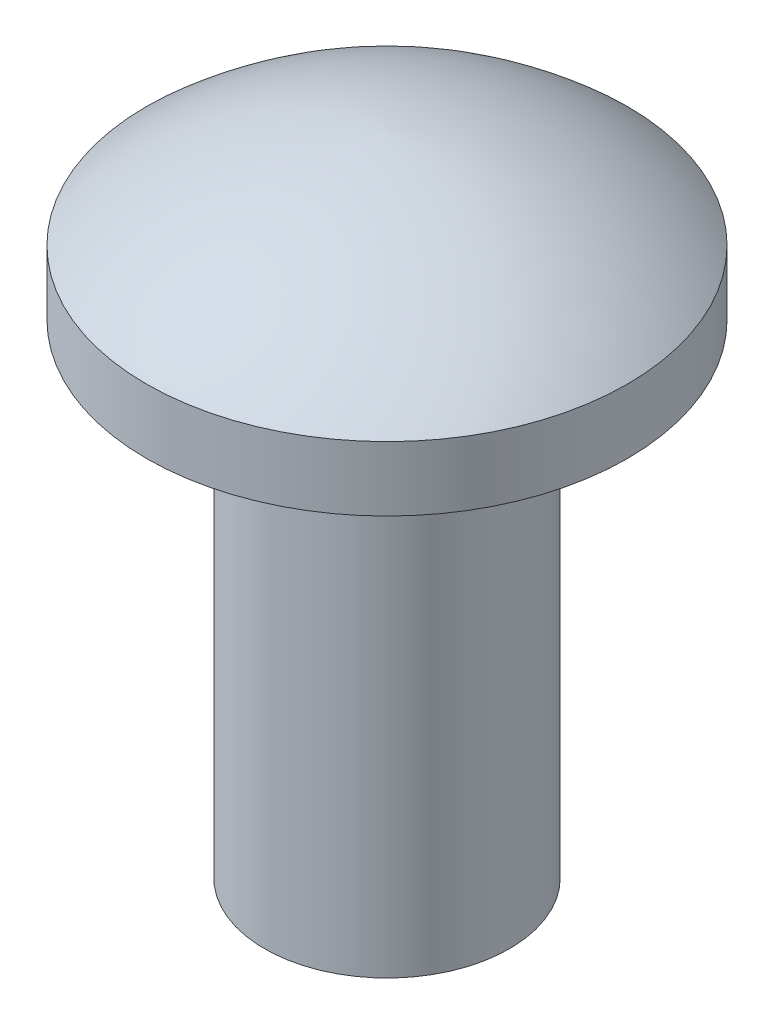
SolidWorks part; units mm, degrees
ref_plane "Front Plane" through (0, 0, 0) normal (0, 0, 1) x (1, 0, 0)
ref_plane "Top Plane" through (0, 0, 0) normal (0, 1, 0) x (1, 0, 0)
ref_plane "Right Plane" through (0, 0, 0) normal (1, 0, 0) x (0, 0, -1)
other "Center of Mass"
sketch "Sketch1" plane through (0, 0, 0) normal (0, 0, 1) x (1, 0, 0)
  line L0 (0, 0) -> (0, 12.7)
  line L1 (0, 0) -> (2.413, 0)
  line L2 (2.413, 0) -> (2.413, 9.525)
  line L3 (2.413, 9.525) -> (4.7371, 9.525)
  line L4 (4.7371, 9.525) -> (4.7371, 10.795)
  line L7 (0, 0) -> (0, 12.7) construction
  arc A0 (0, 12.7) -> (4.7371, 10.795) centre (-0.3504, 4.9864) cw
  dimension "D3" = 4.7371
  dimension "D6" = 7.7216
  dimension "D1" = 12.7
  dimension "D2" = 2.413
  dimension "D4" = 9.525
  dimension "D5" = 1.27
revolve "Revolve1" add sketch "Sketch1" angle 360 about L7
